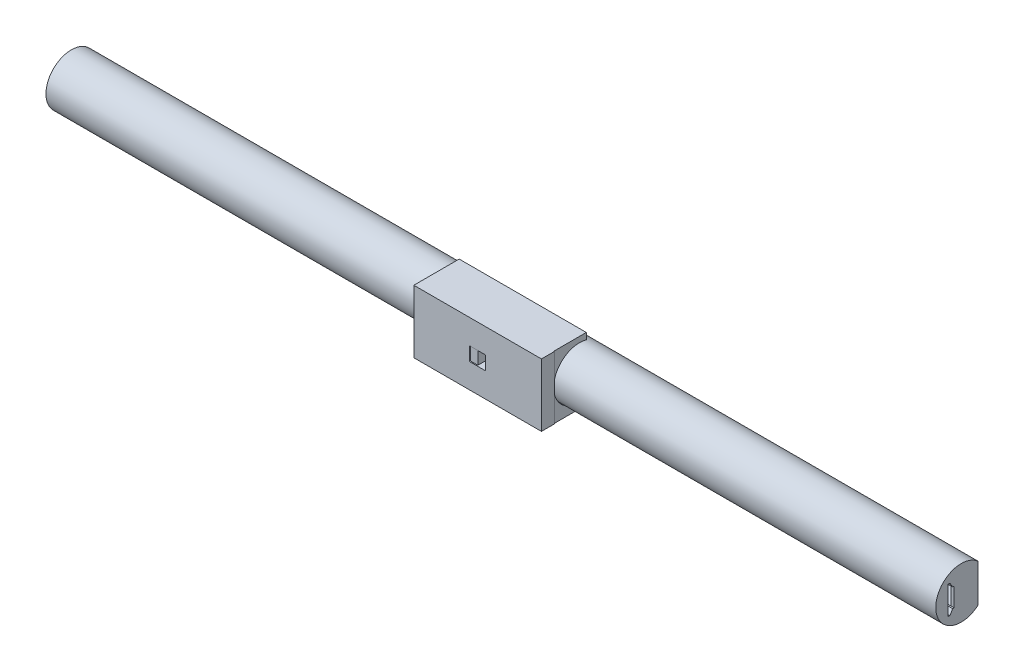
SolidWorks part; units mm, degrees
ref_plane "Front Plane" through (0, 0, 0) normal (0, 0, 1) x (1, 0, 0)
ref_plane "Top Plane" through (0, 0, 0) normal (0, 1, 0) x (1, 0, 0)
ref_plane "Right Plane" through (0, 0, 0) normal (1, 0, 0) x (0, 0, -1)
sketch "NewBarProfile" plane through (0, 0, 0) normal (1, 0, 0) x (0, 1, 0)
  line L0 (7.5, -6.6144) -> (-7.5, -6.6144) construction
  line L1 (-7.5, -6.6144) -> (-6.3, -6.6144)
  line L2 (-6.3, -6.6144) -> (-6.3, 1.2617)
  line L3 (-6.3, 1.2617) -> (0, 4.899) construction
  line L4 (5, 4.899) -> (-5, 4.899) construction
  line L5 (0, -14.4444) -> (0, 14.4444) construction
  line L6 (-5.5, 5.199) -> (5.5, 5.199)
  line L7 (-6.3, 1.2617) -> (-3.7026, 2.7613)
  line L8 (0, 0) -> (-7.1429, 6.9985) construction
  line L9 (-5.5, 4.399) -> (-3.7026, 3.3613)
  line L10 (-5.5, 5.199) -> (-5.5, 4.399)
  line L11 (-3.7026, 3.3613) -> (-3.7026, 2.7613)
  line L12 (7.5, -6.6144) -> (6.3, -6.6144)
  line L13 (3.7026, 3.3613) -> (3.7026, 2.7613)
  line L14 (5.5, 5.199) -> (5.5, 4.399)
  line L15 (5.5, 4.399) -> (3.7026, 3.3613)
  line L16 (6.3, 1.2617) -> (3.7026, 2.7613)
  line L17 (6.3, -6.6144) -> (6.3, 1.2617)
  line L18 (0, -11) -> (0, 11) construction
  circle A0 centre (0, 0) radius 10 construction
  arc A1 (-7.5, -6.6144) -> (7.5, -6.6144) centre (0, 0) cw
  arc A2 (-6.6144, -7.5) -> (-6.6144, 7.5) centre (0, 0) ccw construction
  point P11 (0, 4.899)
  point P14 (0, 0)
sketch "Sketch5" plane through (0, 0, 3.7) normal (1, 0, 0) x (0, 1, 0)
  line L0 (0, -16.5814) -> (0, 9.1814) construction
  line L5 (-7.5, -2.6947) -> (-6.4, -4.6) construction
  line L6 (7.5, -2.6947) -> (6.4, -4.6) construction
  line L7 (5.3668, 1) -> (7.5, -2.6947) construction
  line L8 (-5.3668, 1) -> (5.3668, 1) construction
  line L9 (-5.3668, 1) -> (-7.5, -2.6947) construction
  line L10 (7.7309, -2.6947) -> (6.5732, -4.7)
  line L11 (5.4823, 1.2) -> (7.7309, -2.6947)
  line L12 (-5.4823, 1.2) -> (5.4823, 1.2)
  line L13 (-5.4823, 1.2) -> (-7.7309, -2.6947)
  line L14 (-7.7309, -2.6947) -> (-6.5732, -4.7)
  line L15 (-6.5732, -4.7) -> (6.5732, -4.7)
  line L17 (0, -9.7207) -> (0, 9.7207) construction
  line L18 (-6.9, -10.9381) -> (6.9, -10.9381)
  line L19 (0, -10.9381) -> (0, -3.7) construction
  circle A0 centre (0, -3.7) radius 10 construction
  arc A1 (-6.9, -10.9381) -> (6.9, -10.9381) centre (0, -3.7) cw
  point P18 (0, -13.7)
sketch "Sketch8" plane through (0, 0, 3.7) normal (0, -1, 0) x (1, 0, 0)
  line L2 (0, -9.7207) -> (-145, -9.7207)
  line L3 (0, -9.9381) -> (-145, -9.9381)
  line L4 (0, -10.9381) -> (-150, -10.9381)
  point P0 (0, -9.7207)
  point P3 (0, -10.9381)
sketch "Sketch9" plane through (0, 0, 3.7) normal (1, 0, 0) x (0, 1, 0)
  line L0 (-6.9, -10.9381) -> (6.9, -10.9381) construction
  line L3 (-6.9, -10.9381) -> (6.9, -10.9381) construction
  line L4 (-6.4874, -9.9381) -> (6.4874, -9.9381)
  line L5 (-6.4017, -9.7381) -> (6.4017, -9.7381)
  arc A3 (6.9, -10.9381) -> (-6.9, -10.9381) centre (0, -3.7) ccw construction
  arc A4 (6.4874, -9.9381) -> (-6.4874, -9.9381) centre (0, -3.7) ccw
  arc A5 (6.4017, -9.7381) -> (-6.4017, -9.7381) centre (0, -3.7) ccw
sketch "Sketch1" plane through (0, 0, 0) normal (1, 0, 0) x (0, 0, -1)
  line L63 (-5.199, 5.5) -> (-4.399, 5.5)
  line L64 (-4.399, 5.5) -> (-3.3613, 3.7026)
  line L65 (-3.3613, 3.7026) -> (-2.7613, 3.7026)
  line L66 (-2.7613, 3.7026) -> (-1.2617, 6.3)
  line L67 (-1.2617, 6.3) -> (6.6144, 6.3)
  line L68 (6.6144, 6.3) -> (6.6144, 7.5)
  line L69 (6.6144, -7.5) -> (6.6144, -6.3)
  line L70 (6.6144, -6.3) -> (-1.2617, -6.3)
  line L71 (-1.2617, -6.3) -> (-2.7613, -3.7026)
  line L72 (-2.7613, -3.7026) -> (-3.3613, -3.7026)
  line L73 (-3.3613, -3.7026) -> (-4.399, -5.5)
  line L74 (-4.399, -5.5) -> (-5.199, -5.5)
  line L75 (-5.199, -5.5) -> (-5.199, 5.5)
  line L76 (-5.199, 5.5) -> (-4.399, 5.5)
  line L77 (-4.399, 5.5) -> (-3.3613, 3.7026)
  line L78 (-3.3613, 3.7026) -> (-2.7613, 3.7026)
  line L79 (-2.7613, 3.7026) -> (-1.2617, 6.3)
  line L80 (-1.2617, 6.3) -> (6.6144, 6.3)
  line L81 (6.6144, 6.3) -> (6.6144, 7.5)
  line L82 (6.6144, -7.5) -> (6.6144, -6.3)
  line L83 (6.6144, -6.3) -> (-1.2617, -6.3)
  line L84 (-1.2617, -6.3) -> (-2.7613, -3.7026)
  line L85 (-2.7613, -3.7026) -> (-3.3613, -3.7026)
  line L86 (-3.3613, -3.7026) -> (-4.399, -5.5)
  line L87 (-4.399, -5.5) -> (-5.199, -5.5)
  line L88 (-5.199, -5.5) -> (-5.199, 5.5)
  arc A9 (6.6144, 7.5) -> (6.6144, -7.5) centre (0, 0) ccw
  arc A10 (6.6144, 7.5) -> (6.6144, -7.5) centre (0, 0) ccw
  dimension "D1" = 0
extrude "Bar" add sketch "Sketch1" against normal mid plane 350
sketch "Sketch13" plane through (0, 0, -6.6144) normal (0, 0, -1) x (-1, 0, 0)
  line L0 (175, 7.5) -> (175, -7.5)
  line L1 (175, -7.5) -> (173.8, -7.5)
  line L2 (175, -7.5) -> (-175, -7.5) construction
  line L3 (173.8, -7.5) -> (173.8, 7.5)
  line L4 (175, 7.5) -> (-175, 7.5) construction
  line L5 (173.8, 7.5) -> (175, 7.5)
  line L6 (125.4, 7.5) -> (124.6, 7.5)
  line L7 (124.6, 7.5) -> (124.6, -7.5)
  line L8 (124.6, -7.5) -> (125.4, -7.5)
  line L9 (125.4, -7.5) -> (125.4, 7.5)
  line L10 (125, 7.5) -> (125, -7.5) construction
  line L11 (75.4, -7.5) -> (75.4, 7.5)
  line L12 (75.4, 7.5) -> (74.6, 7.5)
  line L13 (74.6, 7.5) -> (74.6, -7.5)
  line L14 (74.6, -7.5) -> (75.4, -7.5)
  line L15 (25.4, -7.5) -> (25.4, 7.5)
  line L16 (25.4, 7.5) -> (24.6, 7.5)
  line L17 (24.6, 7.5) -> (24.6, -7.5)
  line L18 (24.6, -7.5) -> (25.4, -7.5)
  line L19 (-24.6, -7.5) -> (-24.6, 7.5)
  line L20 (-24.6, 7.5) -> (-25.4, 7.5)
  line L21 (-25.4, 7.5) -> (-25.4, -7.5)
  line L22 (-25.4, -7.5) -> (-24.6, -7.5)
  line L23 (-74.6, -7.5) -> (-74.6, 7.5)
  line L24 (-74.6, 7.5) -> (-75.4, 7.5)
  line L25 (-75.4, 7.5) -> (-75.4, -7.5)
  line L26 (-75.4, -7.5) -> (-74.6, -7.5)
  line L27 (-124.6, -7.5) -> (-124.6, 7.5)
  line L28 (-124.6, 7.5) -> (-125.4, 7.5)
  line L29 (-125.4, 7.5) -> (-125.4, -7.5)
  line L30 (-125.4, -7.5) -> (-124.6, -7.5)
  line L31 (0, -34.8434) -> (0, 34.8434) construction
  line L32 (-173.8, -7.5) -> (-173.8, 7.5)
  line L33 (-175, -7.5) -> (-173.8, -7.5)
  line L34 (-175, 7.5) -> (-175, -7.5)
  line L35 (-173.8, 7.5) -> (-175, 7.5)
  point P40 (0, 0)
  dimension "D1" = 1.2
  dimension "D2" = 0.8
  dimension "D3" = 50
  dimension "D5" = 50
  dimension "D4" = 6
extrude "Boss-Extrude1" add sketch "Sketch13" against normal up to vertex (9.3756 mm away) up to point (175, 3.7026, 2.7613)
sketch "Sketch14" plane through (0, 0, 0) normal (0, 1, 0) x (1, 0, 0)
  line L0 (0, 19.6952) -> (0, -19.6952) construction
  line L2 (-175, -10) -> (175, -10) construction
  line L3 (0.1, 6.6144) -> (-0.1, 6.6144)
  line L5 (0.1, 6.6144) -> (0.1, -10)
  line L7 (0.1, -10) -> (-0.1, -10)
  line L8 (-0.1, 6.6144) -> (-0.1, -10)
  line L9 (0.1, 6.6144) -> (-0.1, -10) construction
  line L10 (0.1, -10) -> (-0.1, 6.6144) construction
  line L11 (-175, 6.6144) -> (175, 6.6144) construction
  point P0 (0, -1.6928)
  point P3 (0, 0)
  dimension "D1" = 0.2
extrude "Cut-Extrude1" cut sketch "Sketch14" against normal through all both and the other way through all
sketch "Sketch15" plane through (0, 0, 0) normal (0, 1, 0) x (1, 0, 0)
  line L0 (-0.1, -8) -> (-0.1, -15)
  line L1 (-0.1, -15) -> (-3.1, -15)
  line L2 (-3.1, -15) -> (-10.1, -8)
  line L3 (-10.1, -8) -> (-0.1, -8)
  point P3 (-0.1, -10)
  dimension "D1" = 2
  dimension "D2" = 5
  dimension "D3" = 45
  dimension "D4" = 3
extrude "Boss-Extrude2" add sketch "Sketch15" along normal mid plane 5
sketch "Sketch16" plane through (-0.1, 0, 0) normal (1, 0, 0) x (0, 0, -1)
  line L48 (2.64, 9.8524) -> (2.64, 12.3524)
  line L49 (2.64, 12.3524) -> (-15.2, 12.3524)
  line L50 (-15.2, 12.3524) -> (-15.2, 2.7)
  line L51 (2.64, 9.8524) -> (8.4798, 8.2877)
  line L52 (-12.3198, 0) -> (12.3198, 0) construction
  line L53 (-15.2, -12.3524) -> (-15.2, -2.7)
  line L54 (2.64, -12.3524) -> (-15.2, -12.3524)
  line L55 (2.64, -9.8524) -> (2.64, -12.3524)
  line L56 (-9.8362, -2.7) -> (-15.2, -2.7)
  line L64 (-9.8362, 2.7) -> (-15.2, 2.7)
  line L65 (-15.2, 2.7) -> (-15.2, -2.7)
  line L66 (-15.2, -2.7) -> (-9.8362, -2.7)
  line L67 (6.8144, -7.5897) -> (6.8144, -6.1)
  line L68 (6.8144, -6.1) -> (-1.1462, -6.1)
  line L69 (-1.1462, -6.1) -> (-2.6458, -3.5026)
  line L70 (-2.6458, -3.5026) -> (-3.4767, -3.5026)
  line L71 (-3.4767, -3.5026) -> (-4.5144, -5.3)
  line L72 (-4.5144, -5.3) -> (-4.999, -5.3)
  line L73 (-4.999, -5.3) -> (-4.999, 5.3)
  line L74 (-4.999, 5.3) -> (-4.5144, 5.3)
  line L75 (-4.5144, 5.3) -> (-3.4767, 3.5026)
  line L76 (-3.4767, 3.5026) -> (-2.6458, 3.5026)
  line L77 (-2.6458, 3.5026) -> (-1.1462, 6.1)
  line L78 (-1.1462, 6.1) -> (6.8144, 6.1)
  line L79 (6.8144, 6.1) -> (6.8144, 7.5897)
  line L80 (-9.8362, 2.7) -> (-15.2, 2.7)
  arc A6 (-9.8362, 2.7) -> (2.64, 9.8524) centre (0, 0) cw
  arc A7 (-9.8362, -2.7) -> (2.64, -9.8524) centre (0, 0) ccw
  arc A8 (6.8144, 7.5897) -> (-9.8362, 2.7) centre (0, 0) ccw
  arc A9 (-9.8362, -2.7) -> (6.8144, -7.5897) centre (0, 0) ccw
  arc A10 (6.8144, 7.5897) -> (-9.8362, 2.7) centre (0, 0) ccw construction
  point P7 (0, 0)
  dimension "D2" = 105
  dimension "D3" = 2.5
  dimension "D1" = 0.2
extrude "Boss-Extrude3" add sketch "Sketch16" along normal mid plane 50 separate body contours A7 L56 L53 L54 L55 | L80 A6 L48 L49 L50 region at (-0.1, 8.6976, 9.0666) region at (-0.1, -8.6976, 9.0666)
sketch "Sketch17" plane through (0, 0, 0) normal (0, 1, 0) x (1, 0, 0)
  line L0 (-25.1, -10.1) -> (-8.2828, -10.1)
  line L2 (-8.2828, -10.1) -> (0, -10.1) construction
  line L4 (-25.1, -15.2) -> (-3.1828, -15.2)
  line L5 (-3.1828, -15.2) -> (-8.2828, -10.1)
  line L7 (0, -19.9979) -> (0, 19.9979) construction
  line L8 (0.1, -15.2) -> (0.1, -7.8)
  line L9 (-3.1828, -15.2) -> (0.1, -15.2)
  line L10 (-10.5828, -7.8) -> (-3.1828, -15.2)
  line L11 (0.1, -7.8) -> (-10.5828, -7.8)
  line L12 (0.1, -15.2) -> (0.1, -7.8) construction
  line L13 (-3.1828, -15.2) -> (0.1, -15.2) construction
  line L14 (-10.5828, -7.8) -> (-3.1828, -15.2) construction
  line L15 (0.1, -7.8) -> (-10.5828, -7.8) construction
  line L16 (-25.1, -9.8362) -> (-25.1, -15.2)
  line L17 (-25.1, -15.2) -> (24.9, -15.2)
  line L18 (24.9, -15.2) -> (24.9, -9.8362)
  line L19 (24.9, -9.8362) -> (-25.1, -9.8362)
  line L20 (-25.1, -10.1) -> (-25.1, -15.2)
  line L24 (8.2828, -10.1) -> (25.1, -10.1)
  line L25 (3.1828, -15.2) -> (8.2828, -10.1)
  line L26 (25.1, -15.2) -> (3.1828, -15.2)
  line L27 (25.1, -10.1) -> (25.1, -15.2)
  circle A0 centre (0, 0) radius 10.1 construction
  point P12 (0, 0)
  dimension "D3" = 20.2
  dimension "D1" = 0.2
  dimension "D2" = 0
extrude "Boss-Extrude4" add sketch "Sketch17" along normal through all and the other way through all
sketch "Sketch18" plane through (0, 0, -6.6144) normal (0, 0, -1) x (-1, 0, 0)
  line L0 (0.1, 7.5) -> (0.1, -7.5)
  line L1 (0.1, -7.5) -> (1.3, -7.5)
  line L2 (175, -7.5) -> (0.1, -7.5) construction
  line L3 (1.3, -7.5) -> (1.3, 7.5)
  line L4 (175, 7.5) -> (0.1, 7.5) construction
  line L5 (1.3, 7.5) -> (0.1, 7.5)
  dimension "D1" = 1.2
extrude "Boss-Extrude5" add sketch "Sketch18" against normal blind 0.2
